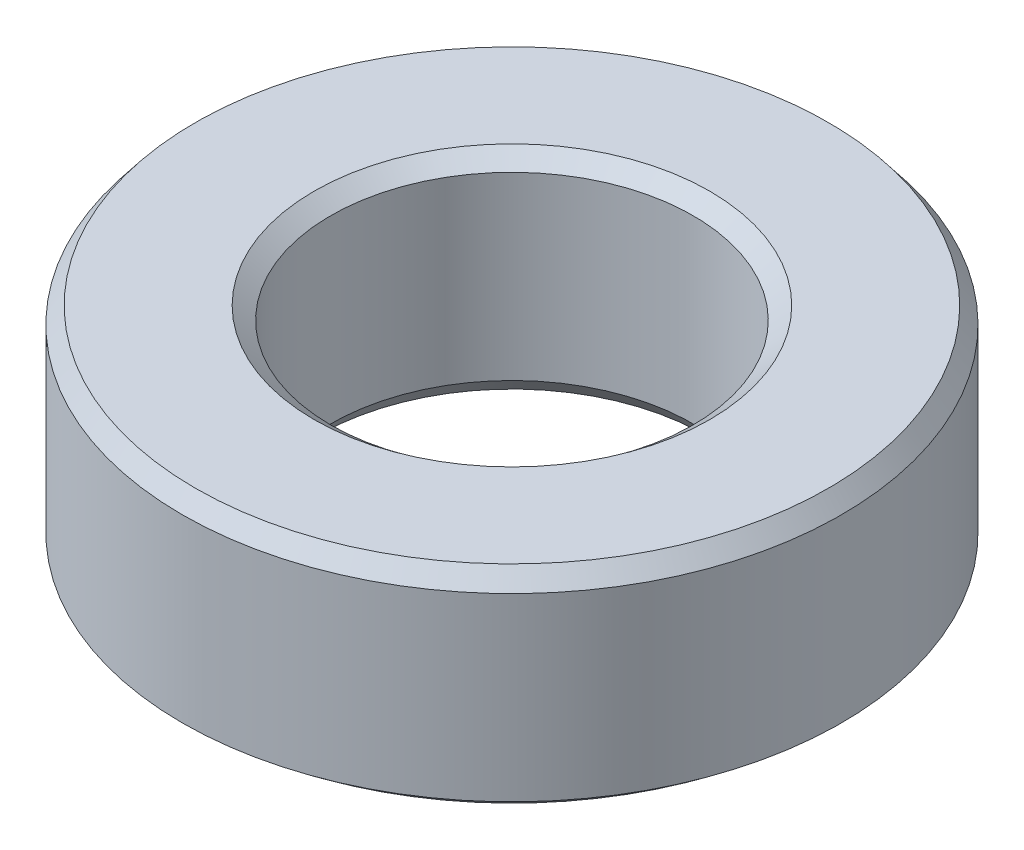
SolidWorks part; units mm, degrees
ref_plane "Front Plane" through (0, 0, 0) normal (0, 0, 1) x (1, 0, 0)
ref_plane "Top Plane" through (0, 0, 0) normal (0, 1, 0) x (1, 0, 0)
ref_plane "Right Plane" through (0, 0, 0) normal (1, 0, 0) x (0, 0, -1)
sketch "Sketch1" plane through (0, 0, 0) normal (0, 1, 0) x (1, 0, 0)
  circle A0 centre (0, 0) radius 50
  dimension "SLEEVE_OD" = 100
extrude "Boss-Extrude1" add sketch "Sketch1" along normal blind 31.8293
sketch "Sketch2" plane through (0, 0, 0) normal (0, 1, 0) x (1, 0, 0)
  circle A0 centre (0, 0) radius 27.5017
  dimension "BORE_D" = 55.0034
extrude "Cut-Extrude1" cut sketch "Sketch2" along normal through all
chamfer "Chamfer1" distance 2.5165 angle 37.917 4 edges at (0, 31.8293, 27.5017) (0, 0, 27.5017) (0, 0, 50) (0, 31.8293, 50) first distance on face at (0, 31.8293, 27.5017) first distance on face at (0, 0, 27.5017) first distance on face at (0, 31.8293, 50)
